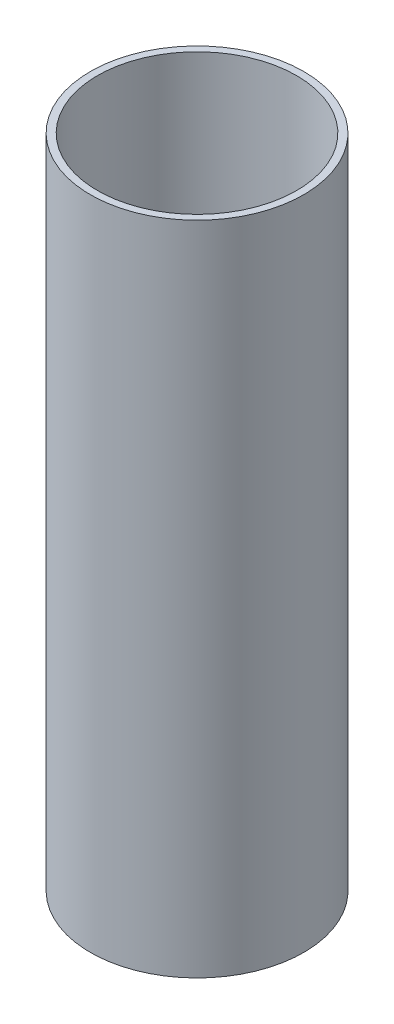
SolidWorks part; units mm, degrees
material "Hexcel AS4C (3000 Filaments)"
ref_plane "Front Plane" through (0, 0, 0) normal (0, 0, 1) x (1, 0, 0)
ref_plane "Top Plane" through (0, 0, 0) normal (0, 1, 0) x (1, 0, 0)
ref_plane "Right Plane" through (0, 0, 0) normal (1, 0, 0) x (0, 0, -1)
sketch "Sketch1" plane through (0, 0, 0) normal (0, 0, 1) x (1, 0, 0)
  line L0 (0, 0) -> (0, 43.8892) construction
  line L1 (26.9875, 25.1886) -> (28.9179, 25.1886)
  line L2 (26.9875, 25.1886) -> (26.9875, -152.6114)
  line L3 (26.9875, -152.6114) -> (28.9179, -152.6114)
  line L4 (28.9179, 25.1886) -> (28.9179, -152.6114)
revolve "Revolve1" add sketch "Sketch1" angle 360 about L0
